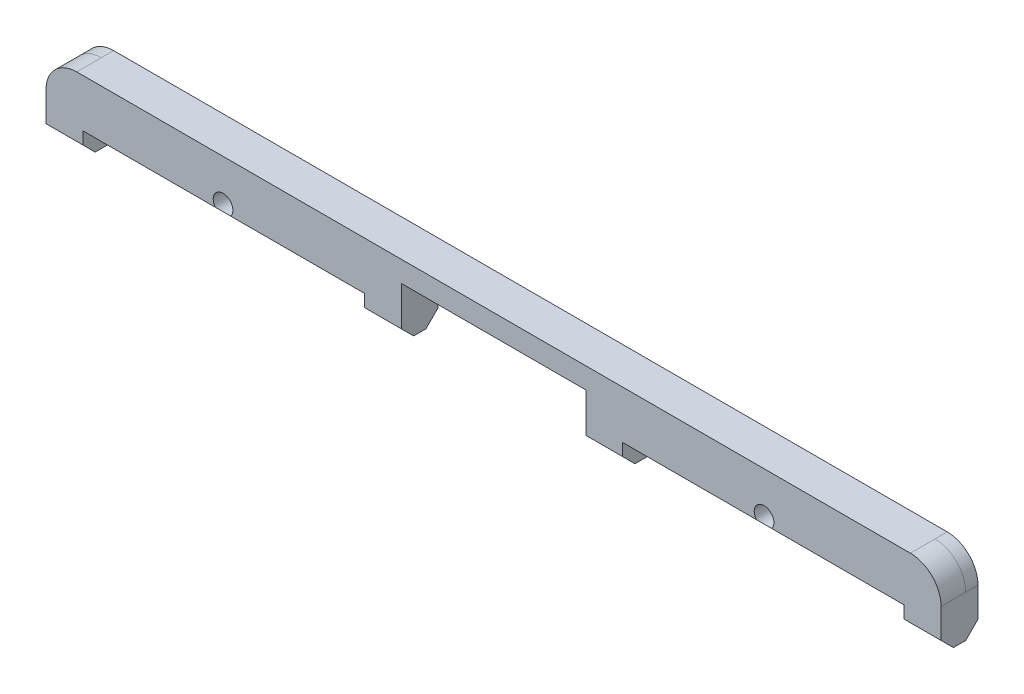
SolidWorks part; units mm, degrees
material "6061-T6 (SS)"
ref_plane "Front Plane" through (0, 0, 0) normal (0, 0, 1) x (1, 0, 0)
ref_plane "Top Plane" through (0, 0, 0) normal (0, 1, 0) x (1, 0, 0)
ref_plane "Right Plane" through (0, 0, 0) normal (1, 0, 0) x (0, 0, -1)
sketch "Sketch1" plane through (0, 0, 0) normal (1, 0, 0) x (0, 0, -1)
  line L0 (-3.0983, 0) -> (1.226, 0) construction
  line L1 (0, -3.2) -> (-2, -1.2)
  line L2 (0, -3.2) -> (0, 3.2)
  line L4 (-2, -1.2) -> (-2, 3.2)
  line L5 (-2, 3.2) -> (0, 3.2)
  dimension "D1" = 2
  dimension "D2" = 45
  dimension "D3" = 6.4
extrude "Boss-Extrude1" add sketch "Sketch1" along normal mid plane 72.8
fillet "Fillet3" radius 2.5 2 edges at (-36.4, 3.2, 1) (36.4, 3.2, 1)
sketch "Sketch5" plane through (-36.4, 0, 0) normal (-1, 0, 0) x (0, 0, 1)
  line L0 (0, -2.7) -> (2, -0.7)
  line L1 (0, -3.2) -> (0, 0.7) construction
  line L2 (2, 0.7) -> (2, -1.2) construction
  line L3 (2, -1.2) -> (0, -3.2) construction
  line L4 (2, -1.2) -> (2, -0.7)
  line L5 (2, -1.2) -> (0, -3.2)
  line L6 (0, -3.2) -> (0, -2.7)
  dimension "D1" = 0.5
extrude "Cut-Extrude5" cut sketch "Sketch5" against normal up to surface (72.8 mm away) up to face at (36.4, -0.75, 1)
sketch "Sketch7" plane through (-36.4, 0, 0) normal (-1, 0, 0) x (0, 0, 1)
  line L0 (0, -2.7) -> (-1, -1.7)
  line L1 (-1, -1.7) -> (-1, 3.2)
  line L2 (-1, 3.2) -> (0, 3.2)
  line L3 (0, 3.2) -> (0, -2.7)
  line L4 (0, 3.2) -> (2, 3.2) construction
  dimension "D1" = 45
  dimension "D2" = 3
extrude "Boss-Extrude2" add sketch "Sketch7" against normal up to surface (72.8 mm away) up to face at (36.4, -0.5, 1)
hole_wizard "M2x0.4 Tapped Hole1" positions "Sketch2" profile "Sketch3" tap size "M2x0.4" standard "ANSI Metric"
sketch "Sketch2" plane through (0, 0, 2) normal (0, 0, 1) x (1, 0, 0)
  circle A4 centre (-22, -0.2) radius 1.2 construction
  circle A5 centre (-22, -0.2) radius 1.2
  circle A8 centre (22, -0.2) radius 1.2 construction
  circle A9 centre (22, -0.2) radius 1.2
  circle A10 centre (0, -0.2) radius 1.2
  point P22 (-22, -0.2)
  point P28 (22, -0.2)
  point P31 (0, -0.2)
cosmetic thread "Hole Thread4" parameters "D1"=3, "D2"=2
cosmetic thread "Hole Thread6" parameters "D1"=3, "D2"=2
sketch "Sketch3" plane through (-22, -0.2, 2) normal (1, 0, 0) x (0, -1, 0)
  line L0 (0, 0) -> (0, 4.0807)
  line L1 (0, 4.0807) -> (0.8, 3.6)
  line L2 (0.8, 3.6) -> (0.8, 0)
  line L5 (0.8, 0) -> (0, 0)
  line L10 (0, 4.0807) -> (-0.8, 3.6) construction
  line L11 (0, -6.35) -> (0, 107.95) construction
  dimension "Tap Drill Dia." = 1.6
  dimension "Tap Drill Depth" = 3.6
  dimension "Drill Angle" = 118
cosmetic thread "Hole Thread7" parameters "D1"=3, "D2"=2
fillet "Fillet4" radius 2.5 2 edges at (-36.4, 3.2, -0.5) (36.4, 3.2, -0.5)
sketch "Sketch4" plane through (0, 0, 0) normal (0, 0, 1) x (1, 0, 0)
  line L1 (7.5, 1.5) -> (-7.5, 1.5)
  line L2 (7.5, 1.5) -> (7.5, -3.2)
  line L3 (7.5, -3.2) -> (-7.5, -3.2)
  line L4 (-7.5, 1.5) -> (-7.5, -3.2)
  line L5 (0, 7.7759) -> (0, -8.8374) construction
  line L8 (-7.5, -1.7) -> (-7.5, -0.7) construction
  dimension "D1" = 4.7
extrude "Cut-Extrude4" cut sketch "Sketch4" along normal mid plane 10
sketch "Sketch8" [suppressed] plane through (36.4, 0, 0) normal (1, 0, 0) x (0, 0, -1)
  line L1 (-1, -3.2) -> (-2, -2.2)
  line L2 (-2, -2.2) -> (-2, -1.2)
  line L3 (-2, -1.2) -> (0, -3.2)
  line L4 (0, -3.2) -> (-1, -3.2)
  dimension "D1" = 1
extrude "Boss-Extrude3" [suppressed] add sketch "Sketch8" against normal blind 3
sketch "Sketch10" [suppressed] plane through (7.5, 0, 0) normal (-1, 0, 0) x (0, 0, 1)
  line L1 (1, -3.2) -> (2, -2.2)
  line L2 (2, -2.2) -> (2, -1.2)
  line L3 (2, -1.2) -> (0, -3.2)
  line L4 (2, -2.2) -> (1, -3.2) construction
  line L5 (0, -3.2) -> (1, -3.2)
extrude "Boss-Extrude5" [suppressed] add sketch "Sketch10" against normal blind 3
mirror "Mirror1" [suppressed] about plane through (0, 0, 0) normal (1, 0, 0)
sketch "Sketch11" plane through (36.4, 0, 0) normal (1, 0, 0) x (0, 0, -1)
  line L0 (0, -2.7) -> (-1, -2.7)
  line L1 (-1, -2.7) -> (-2, -1.7)
  line L2 (-2, -1.7) -> (-2, -0.7)
  line L3 (0, -2.7) -> (-2, -0.7)
  dimension "D1" = 1
extrude "Boss-Extrude6" add sketch "Sketch11" against normal blind 3
sketch "Sketch12" plane through (7.5, 0, 0) normal (-1, 0, 0) x (0, 0, 1)
  line L0 (0, -2.7) -> (1, -2.7)
  line L1 (1, -2.7) -> (2, -1.7)
  line L2 (2, -1.7) -> (2, -0.7)
  line L3 (0, -2.7) -> (2, -0.7)
  line L4 (1, -2.7) -> (0, -2.7) construction
  line L5 (2, -1.7) -> (1, -2.7) construction
extrude "Boss-Extrude7" add sketch "Sketch12" against normal blind 3
mirror "Mirror7" about plane through (0, 0, 0) normal (1, 0, 0) of bodies 112 111
sketch "Sketch13" [suppressed] plane through (0, 0, 2) normal (0, 0, 1) x (1, 0, 0)
  line L0 (24.4, 3.2) -> (24.4, -2.7)
  line L1 (33.9, 3.2) -> (-33.9, 3.2) construction
  line L2 (36.4, -2.7) -> (-36.4, -2.7) construction
  line L4 (24.4, -2.7) -> (36.4, -2.7)
  line L5 (36.4, -2.7) -> (36.4, 3.2)
  line L6 (36.4, 3.2) -> (24.4, 3.2)
  dimension "D1" = 12
extrude "Cut-Extrude6" [suppressed] cut sketch "Sketch13" against normal up to surface (3 mm away) up to face at (21.2, -0.2, -1)
